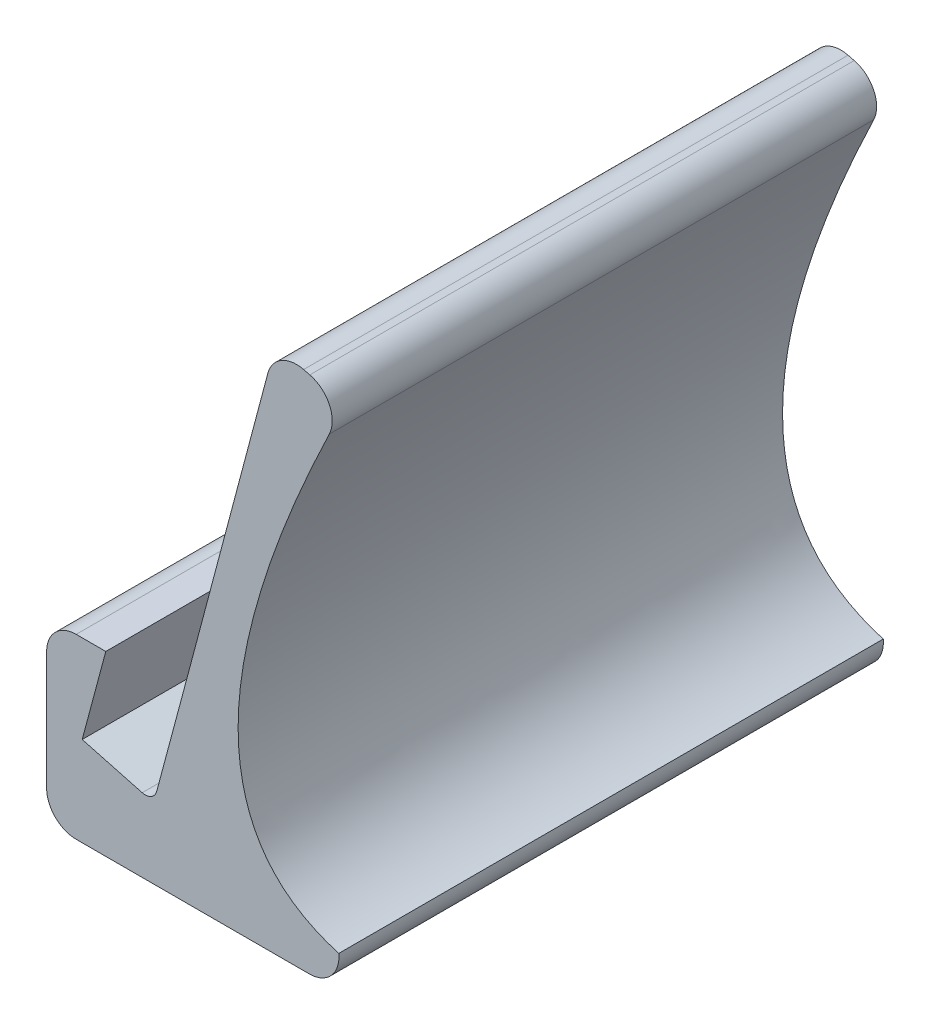
SolidWorks part; units mm, degrees
ref_plane "Ön Düzlem" through (0, 0, 0) normal (0, 0, 1) x (1, 0, 0)
ref_plane "Üst Düzlem" through (0, 0, 0) normal (0, 1, 0) x (1, 0, 0)
ref_plane "Sağ Düzlem" through (0, 0, 0) normal (1, 0, 0) x (0, 0, -1)
sketch "Sketch1" plane through (0, 0, 0) normal (0, 0, 1) x (1, 0, 0)
  line L0 (37.3869, 84.405) -> (22.9336, 30)
  line L1 (5, 0) -> (44.4022, 0)
  line L2 (0, 5) -> (0, 25)
  line L3 (5, 30) -> (10, 30)
  line L4 (10, 30) -> (13.7568, 45.027)
  line L5 (30.1602, 57.2025) -> (22.5084, 59.2012)
  line L6 (10, 30) -> (6.0132, 15.1209)
  line L7 (6.0132, 15.1209) -> (16.1546, 12.4035)
  line L8 (18.6043, 13.8185) -> (22.9336, 30)
  line L9 (21.8623, 50.7315) -> (19.1944, 40.0599) construction
  line L10 (18.7093, 51.5197) -> (17.8605, 48.1242)
  line L11 (43.432, 87.9719) -> (44.4769, 87.7106)
  line L12 (25.0153, 49.9432) -> (22.3474, 39.2717)
  line L13 (18.7093, 51.5197) -> (25.0153, 49.9432)
  line L14 (16.0414, 40.8482) -> (22.3474, 39.2717)
  line L15 (20.5284, 45.3957) -> (10.9173, 47.7985) construction
  line L16 (13.7568, 45.027) -> (16.8903, 44.2436)
  line L17 (17.8605, 48.1242) -> (16.8903, 44.2436)
  line L18 (20.0433, 43.4554) -> (19.1944, 40.0599)
  line L20 (16.8903, 44.2436) -> (16.0414, 40.8482)
  line L21 (18.7093, 51.5197) -> (16.0414, 40.8482) construction
  line L22 (14.7269, 48.9076) -> (16.3941, 55.5762)
  line L23 (16.0414, 40.8482) -> (12.9079, 41.6315)
  line L24 (17.8605, 48.1242) -> (21.0134, 47.336)
  line L25 (14.7269, 48.9076) -> (13.7568, 45.027)
  line L26 (16.8903, 44.2436) -> (20.0433, 43.4554)
  arc A0 (16.1546, 12.4035) -> (18.6043, 13.8185) centre (16.6723, 14.3354) ccw
  arc A1 (0, 25) -> (5, 30) centre (5, 25) cw
  arc A2 (44.4022, 0) -> (49.3769, 5.502) centre (44.4022, 5) ccw
  arc A3 (5, 0) -> (0, 5) centre (5, 5) cw
  arc A4 (37.3869, 84.405) -> (43.432, 87.9719) centre (42.2193, 83.1212) cw
  arc A5 (44.4769, 87.7106) -> (47.769, 80.6903) centre (43.2643, 82.8599) cw
  arc A6 (22.5084, 59.2012) -> (16.3941, 55.5762) centre (21.2448, 54.3635) ccw
  arc A7 (20.0433, 43.4554) -> (21.0134, 47.336) centre (20.5284, 45.3957) ccw
  spline S1 degree 3 poles (47.769, 80.6903) (37.2373, 58.8233) (26.9736, 24.4249) (38.3092, 8.6978) (49.3769, 5.502) knots 0.034365 0.034365 0.034365 0.034365 0.450207 0.866049 0.866049 0.866049 0.866049
  point P11 (18.0872, 11.8857)
  point P15 (0, 30)
  point P22 (0, 0)
  point P30 (20.5284, 45.3957)
  dimension "D5" = 2
  dimension "D6" = 5
  dimension "D1" = 5
  dimension "D11" = 5
  dimension "D2" = 30
  dimension "D3" = 10
  dimension "D4" = 12.5
  dimension "D7" = 33
  dimension "D8" = 11
  dimension "D9" = 3.25
  dimension "D10" = 3.25
extrude "Boss-Extrude1" add sketch "Sketch1" along normal blind 92 contours L11 A4 L0 L8 A0 L7 L6 L3 A1 L2 A3 L1 A2 region at (26.1916, 28.8605, 0)
extrude "Boss-Extrude2" add sketch "Sketch1<3>" along normal blind 5 contours L5 A6 L22 L10 L13 L12 L14 L20 L4 L6 L7 A0 L8 L0 | L10 L20 L14 L12 L13 A7 region at (17.7754, 34.6678, 0) region at (18.4225, 49.7876, 0)
sketch "Sketch1<3>" plane through (0, 0, 0) normal (0, 0, 1) x (1, 0, 0) same geometry as "Sketch1"
extrude "Boss-Extrude3" add sketch "Sketch1<4>" along normal blind 30 from offset 5 contours L5 A6 L22 L10 L13 L12 L14 L20 L4 L6 L7 A0 L8 L0 region at (17.7754, 34.6678, 0)
sketch "Sketch1<4>" plane through (0, 0, 0) normal (0, 0, 1) x (1, 0, 0) same geometry as "Sketch1"
